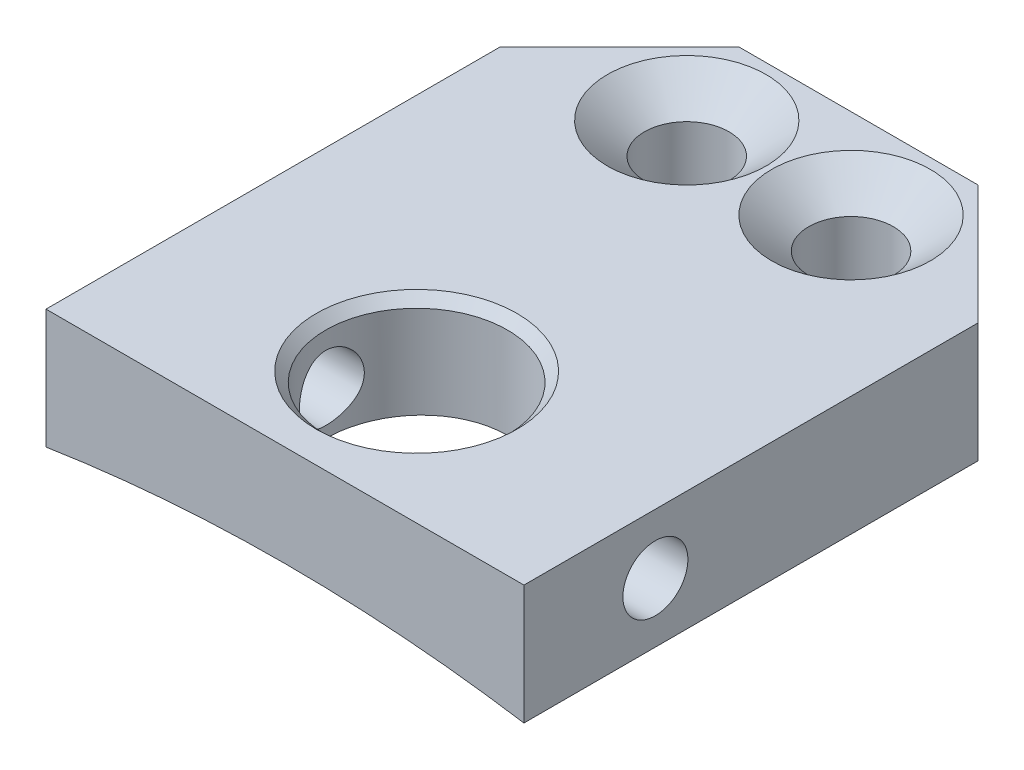
SolidWorks part; units mm, degrees
ref_plane "Front Plane" through (0, 0, 0) normal (0, 0, 1) x (1, 0, 0)
ref_plane "Top Plane" through (0, 0, 0) normal (0, 1, 0) x (1, 0, 0)
ref_plane "Right Plane" through (0, 0, 0) normal (1, 0, 0) x (0, 0, -1)
sketch "Sketch1" plane through (0, 0, 0) normal (0, 1, 0) x (1, 0, 0)
  line L0 (-28.5118, 11.5753) -> (-22.1618, 17.9253)
  line L1 (-22.1618, 17.9253) -> (-9.4618, 17.9253)
  line L2 (-28.5118, 11.5753) -> (-28.5118, -12.5547)
  line L3 (-28.5118, -12.5547) -> (-3.1118, -12.5547)
  line L4 (-3.1118, 11.5753) -> (-3.1118, -12.5547)
  line L5 (-9.4618, 17.9253) -> (-3.1118, 11.5753)
  line L6 (-15.8118, -12.5547) -> (-15.8118, 17.9253) construction
  line L8 (-3.1118, 11.5753) -> (-3.1118, 17.9253) construction
  line L9 (-3.1118, 17.9253) -> (-9.4618, 17.9253) construction
  dimension "D1" = 12.7
  dimension "D2" = 30.48
  dimension "D3" = 25.4
extrude "Boss-Extrude1" add sketch "Sketch1" along normal blind 6.35
sketch "Sketch2" plane through (0, 0, 12.5547) normal (0, 0, 1) x (1, 0, 0)
  circle A0 centre (-15.8118, -81.0531) radius 82.042
  dimension "D1" = 164.084
hole_wizard "CSK for #8 Flat Head Machine Screw (100)1" positions "Sketch3" profile "Sketch4" countersink size "#8" standard "ANSI Inch" end condition through all
sketch "Sketch3" plane through (0, 6.35, 0) normal (0, 1, 0) x (1, 0, 0)
  line L0 (-15.8118, 17.9253) -> (-15.8118, 3.4006) construction
  line L1 (-9.4618, 17.9253) -> (-22.1618, 17.9253) construction
  point P0 (-20.1775, 13.1628)
  point P12 (-11.4462, 13.1628)
  dimension "D1" = 4.7625
  dimension "D2" = 4.3656
sketch "Sketch4" plane through (-20.1775, 6.35, -13.1628) normal (1, 0, 0) x (0, 0, 1)
  line L0 (0, 0) -> (0, 6.35)
  line L1 (0, 6.35) -> (2.2479, 6.35)
  line L2 (2.2479, 6.35) -> (2.2479, 1.6518)
  line L3 (2.2479, 1.6518) -> (4.2164, 0)
  line L5 (4.2164, 0) -> (0, 0)
  line L6 (-2.2479, 1.6518) -> (-4.2164, 0) construction
  line L11 (0, -6.35) -> (0, 107.95) construction
  dimension "Thru Hole Dia." = 4.4958
  dimension "Thru Hole Depth" = 6.35
  dimension "Near C'Sink Dia." = 8.4328
  dimension "Near C'Sink Angle" = 100
extrude "Cut-Extrude1" cut sketch "Sketch2" against normal through all
sketch "Sketch5" plane through (0, 6.35, 0) normal (0, 1, 0) x (1, 0, 0)
  line L1 (-28.5118, 11.5753) -> (-28.5118, -12.5547) construction
  line L2 (-9.4618, 17.9253) -> (-22.1618, 17.9253) construction
  circle A0 centre (-15.7994, -5.5697) radius 1.1303
  dimension "D3" = 2.2606
  dimension "D4" = 12.7124
  dimension "D5" = 23.495
extrude "Cut-Extrude2" cut sketch "Sketch5" against normal through all
sketch "Sketch6" plane through (0, 6.35, 0) normal (0, 1, 0) x (1, 0, 0)
  circle A0 centre (-15.7994, -5.5697) radius 4.826
  dimension "D1" = 9.652
extrude "Cut-Extrude3" cut sketch "Sketch6" against normal through all
chamfer "Chamfer1" distance 0.508 angle 45 1 edges at (-15.7994, 6.35, 10.3957)
hole_wizard "#8-32 Tapped Hole1" positions "Sketch7" profile "Sketch8" tap size "#8-32" standard "ANSI Inch" end condition through all
sketch "Sketch7" plane through (-28.5118, 0, 0) normal (-1, 0, 0) x (0, 0, 1)
  line L0 (10.3957, 5.842) -> (0.7437, 5.842) construction
  line L1 (10.3957, 5.842) -> (0.7437, 5.842)
  line L2 (5.5697, 6.35) -> (5.5697, 0) construction
  line L3 (-11.5753, 6.35) -> (12.5547, 6.35) construction
  line L4 (-11.5753, 0) -> (12.5547, 0) construction
  point P0 (5.5697, 3.175)
  point P12 (5.5697, 5.842)
  point P13 (0, 0)
sketch "Sketch8" plane through (-28.5118, 3.175, 5.5697) normal (0, 1, 0) x (0, 0, 1)
  line L0 (0, 0) -> (0, 25.4)
  line L1 (0, 25.4) -> (1.7272, 25.4)
  line L2 (1.7272, 25.4) -> (1.7272, 0)
  line L5 (1.7272, 0) -> (0, 0)
  line L11 (0, -6.35) -> (0, 107.95) construction
  dimension "Thru Tap Drill Dia." = 3.4544
  dimension "Thru Tap Drill Depth" = 25.4
cosmetic thread "Hole Thread2" parameters "D2"=4.1656
